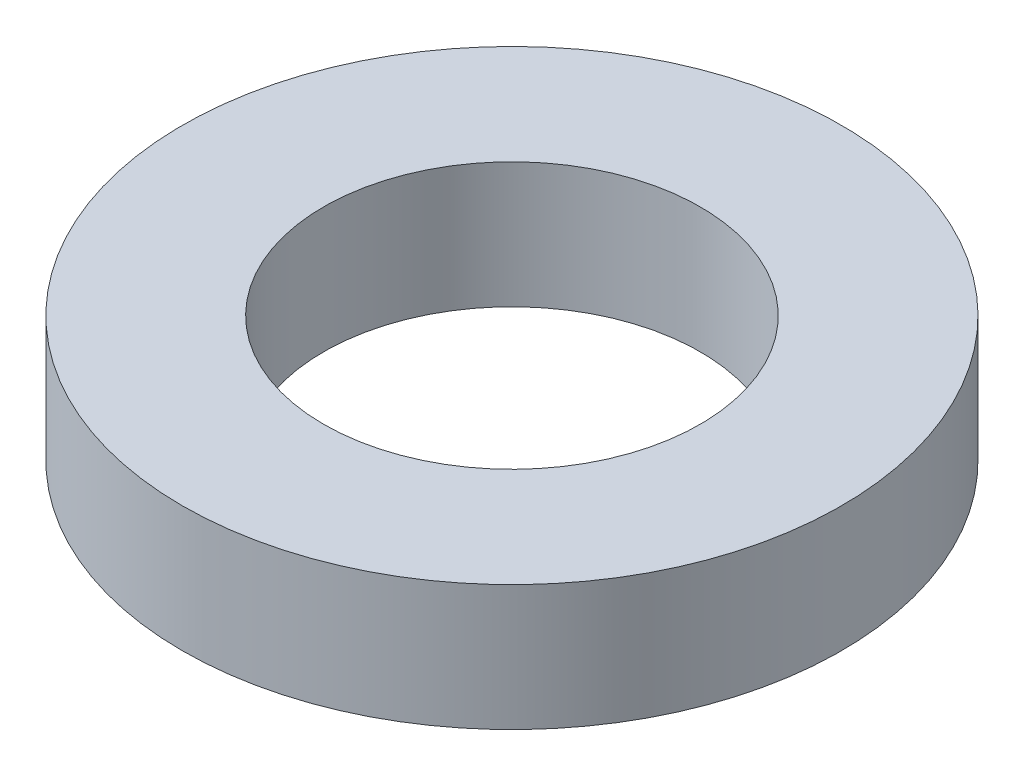
SolidWorks part; units mm, degrees
ref_plane "Front Plane" through (0, 0, 0) normal (0, 0, 1) x (1, 0, 0)
ref_plane "Top Plane" through (0, 0, 0) normal (0, 1, 0) x (1, 0, 0)
ref_plane "Right Plane" through (0, 0, 0) normal (1, 0, 0) x (0, 0, -1)
sketch "Sketch1" plane through (0, 0, 0) normal (0, 1, 0) x (1, 0, 0)
  circle A0 centre (0, 0) radius 52.5
  dimension "FLANGE_OD" = 105
extrude "Boss-Extrude1" add sketch "Sketch1" along normal blind 20
sketch "Sketch2" plane through (0, 0, 0) normal (0, 1, 0) x (1, 0, 0)
  circle A0 centre (0, 0) radius 30
  dimension "BORE_D" = 60
extrude "Cut-Extrude1" cut sketch "Sketch2" along normal through all
sketch "Sketch3" plane through (0, 20, 0) normal (0, 1, 0) x (1, 0, 0)
  circle A0 centre (0, 0) radius 22.0926 construction
  circle A1 centre (-22.0926, 0) radius 3.7304
  dimension "BOLT_D" = 7.4608
  dimension "BOLT_PCD" = 44.1851
extrude "Cut-Extrude2" cut sketch "Sketch3" against normal blind 15.4585 rebuild error yes
pattern_circular "CirPattern1" count 6 over 360 rebuild error yes
